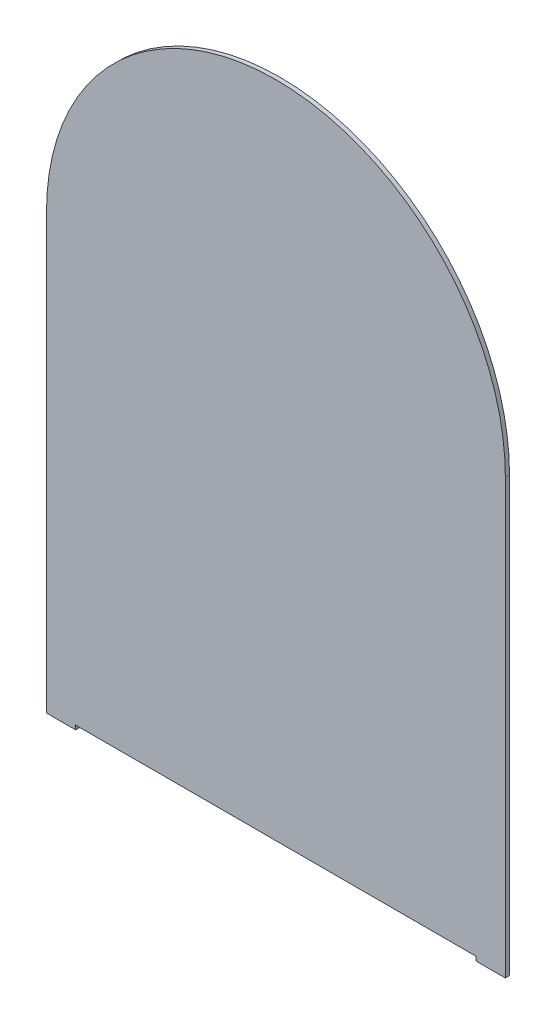
SolidWorks part; units mm, degrees
ref_plane "Front" through (0, 0, 0) normal (0, 0, 1) x (1, 0, 0)
ref_plane "Top" through (0, 0, 0) normal (0, 1, 0) x (1, 0, 0)
ref_plane "Right" through (0, 0, 0) normal (1, 0, 0) x (0, 0, -1)
sketch "Sketch1" plane through (0, 0, 0) normal (0, 0, 1) x (1, 0, 0)
  line L2 (0, 0) -> (0, -330.2)
  line L3 (0, -330.2) -> (349.25, -330.2)
  line L4 (349.25, 0) -> (349.25, -330.2)
  arc A0 (0, 0) -> (349.25, 0) centre (174.625, 0) cw
  dimension "D1" = 330.2
  dimension "D2" = 349.25
extrude "Boss-Extrude1" add sketch "Sketch1" along normal blind 3.175
sketch "Sketch2" plane through (0, 0, 3.175) normal (0, 0, 1) x (1, 0, 0)
  line L0 (0, -330.2) -> (349.25, -330.2) construction
  line L1 (22.225, -327.025) -> (327.025, -327.025)
  line L2 (22.225, -327.025) -> (22.225, -330.2)
  line L3 (22.225, -330.2) -> (327.025, -330.2)
  line L4 (327.025, -327.025) -> (327.025, -330.2)
  point P6 (174.625, -330.2)
  dimension "D1" = 304.8
  dimension "D2" = 3.175
extrude "Cut-Extrude1" cut sketch "Sketch2" against normal blind 3.175
